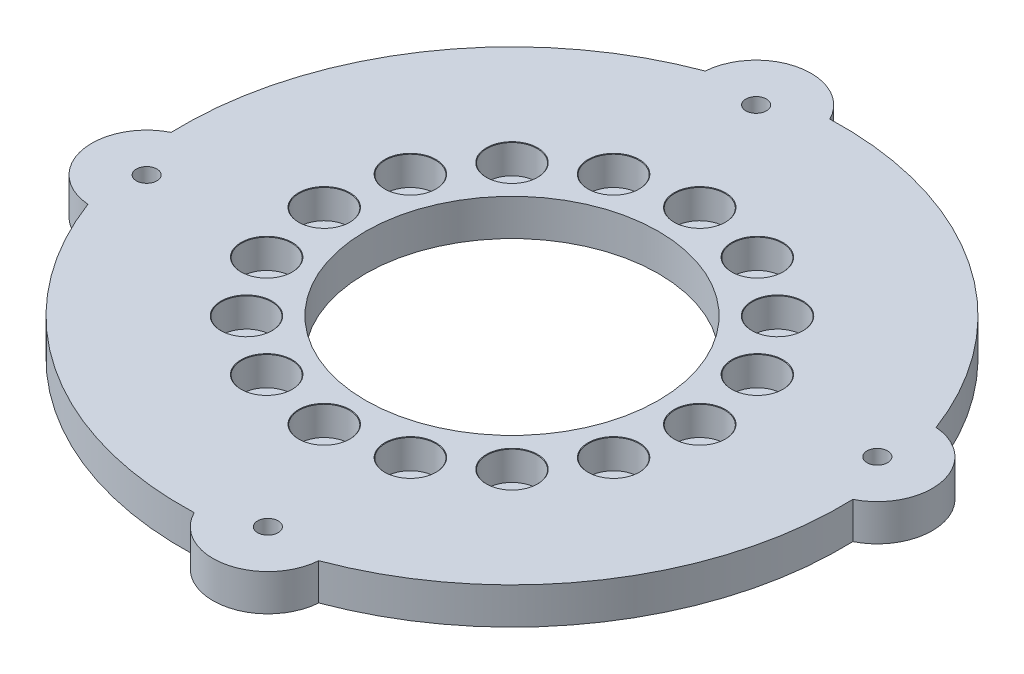
SolidWorks part; units mm, degrees
material "Cast Alloy Steel"
ref_plane "Front Plane" through (0, 0, 0) normal (0, 0, 1) x (1, 0, 0)
ref_plane "Top Plane" through (0, 0, 0) normal (0, 1, 0) x (1, 0, 0)
ref_plane "Right Plane" through (0, 0, 0) normal (1, 0, 0) x (0, 0, -1)
sketch "Sketch1" plane through (0, 0, 0) normal (0, 0, 1) x (1, 0, 0)
  line L0 (114.3, 12.7) -> (114.3, 0)
  line L1 (114.3, 0) -> (50.8, 0)
  line L2 (50.8, 0) -> (50.8, 12.7)
  line L3 (50.8, 12.7) -> (114.3, 12.7)
  line L4 (-86.8914, 0) -> (114.3, 0) construction
  line L5 (0, 58.2054) -> (0, -80.3193) construction
  line L6 (50.8, 6.35) -> (0, 6.35) construction
  line L7 (0, 6.35) -> (114.3, 6.35) construction
  dimension "D1" = 12.7
  dimension "D2" = 50.8
  dimension "D3" = 114.3
revolve "Revolve1" add sketch "Sketch1" angle 360 about L5
ref_axis "Axis1" through (0, 58.2054, 0) along (0, -1, 0)
sketch "Sketch16" plane through (0, 12.7, 0) normal (0, 1, 0) x (1, 0, 0)
  circle A0 centre (0, 0) radius 65.1256
  dimension "D1" = 130.2512
ref_point "Point1"
sketch "Sketch17" plane through (0, 12.7, 0) normal (0, 1, 0) x (1, 0, 0)
  line L0 (0, 0) -> (160.0318, 0) construction
  line L1 (0, 0) -> (99.472, 99.472) construction
  dimension "D1" = 45
hole_wizard "CBORE for 5/16 Binding Head Machine Screw1" positions "Sketch21" profile "Sketch20" counterbore size "5/16" standard "ANSI Inch" end condition through all
sketch "Sketch21" plane through (0, 12.7, 0) normal (0, 1, 0) x (1, 0, 0)
  line L0 (0, 0) -> (160.0318, 0) construction
  circle A0 centre (0, 0) radius 65.1256 construction
  point P0 (65.1256, 0)
sketch "Sketch20" plane through (65.1256, 12.7, 0) normal (1, 0, 0) x (0, 0, 1)
  line L0 (0, 0) -> (0, 12.7)
  line L1 (0, 12.7) -> (4.2164, 12.7)
  line L3 (4.2164, 12.7) -> (4.2164, 10.16)
  line L4 (8.7312, 10.16) -> (4.2164, 10.16)
  line L5 (8.7312, 10.16) -> (8.7312, 0.1588)
  line L6 (8.7312, 0.1588) -> (8.89, 0)
  line L7 (8.89, 0) -> (0, 0)
  line L8 (-8.7312, 0.1587) -> (-8.89, 0) construction
  line L11 (0, -6.35) -> (0, 107.95) construction
  dimension "Thru Hole Dia." = 8.4328
  dimension "Thru Hole Depth" = 12.7
  dimension "C'Bore Dia." = 17.4625
  dimension "C'Bore Depth" = 10.16
  dimension "Near C'Sink Dia." = 17.78
  dimension "Near C'Sink Angle" = 90
pattern_circular "CirPattern1" count 16 over 360 about axis through (0, 58.2054, 0) along (0, -1, 0) of "CBORE for 5/16 Binding Head Machine Screw1"
sketch "Sketch22" plane through (0, 12.7, 0) normal (0, 1, 0) x (1, 0, 0)
  line L0 (0, 0) -> (151.3368, 30.1028) construction
  line L1 (0, 0) -> (160.0318, 0) construction
  dimension "D1" = 11.25
sketch "Sketch23" plane through (0, 12.7, 0) normal (0, 1, 0) x (1, 0, 0)
  line L0 (105.6924, 21.0235) -> (-21.0235, 105.6924)
  line L1 (105.6924, 21.0235) -> (21.0235, -105.6924)
  line L2 (-21.0235, 105.6924) -> (-105.6924, -21.0235)
  line L3 (21.0235, -105.6924) -> (-105.6924, -21.0235)
  line L4 (0, 0) -> (151.3368, 30.1028) construction
  circle A0 centre (0, 0) radius 50.8 construction
  dimension "D1" = 152.4
  dimension "D2" = 152.4
  dimension "D3" = 76.2
  dimension "D4" = 76.2
sketch "Sketch24" plane through (0, 12.7, 0) normal (0, 1, 0) x (1, 0, 0)
  circle A0 centre (-21.0235, 105.6924) radius 19.05
  circle A1 centre (105.6924, 21.0235) radius 19.05
  circle A2 centre (-105.6924, -21.0235) radius 19.05
  circle A3 centre (21.0235, -105.6924) radius 19.05
  dimension "D1" = 38.1
  dimension "D2" = 38.1
  dimension "D3" = 38.1
  dimension "D4" = 38.1
extrude "Boss-Extrude1" add sketch "Sketch24" against normal blind 12.7
hole_wizard "CBORE for 1/4 Binding Head Machine Screw1" positions "Sketch26" profile "Sketch25" counterbore size "1/4" standard "ANSI Inch" end condition through all
sketch "Sketch26" plane through (0, 0, 0) normal (0, -1, 0) x (-1, 0, 0)
  point P0 (-21.0235, -105.6924)
  point P3 (-105.6924, 21.0235)
  point P6 (21.0235, 105.6924)
  point P9 (105.6924, -21.0235)
sketch "Sketch25" plane through (21.0235, 0, 105.6924) normal (1, 0, 0) x (0, 0, -1)
  line L0 (0, 0) -> (0, 12.7)
  line L1 (0, 12.7) -> (3.5712, 12.7)
  line L3 (3.5712, 12.7) -> (3.5712, 4.191)
  line L4 (3.5712, 4.191) -> (7.1437, 4.191)
  line L5 (7.1437, 4.191) -> (7.1437, 0)
  line L7 (7.1437, 0) -> (0, 0)
  line L11 (0, -6.35) -> (0, 107.95) construction
  dimension "Thru Hole Dia." = 7.1425
  dimension "Thru Hole Depth" = 12.7
  dimension "C'Bore Dia." = 14.2875
  dimension "C'Bore Depth" = 4.191
